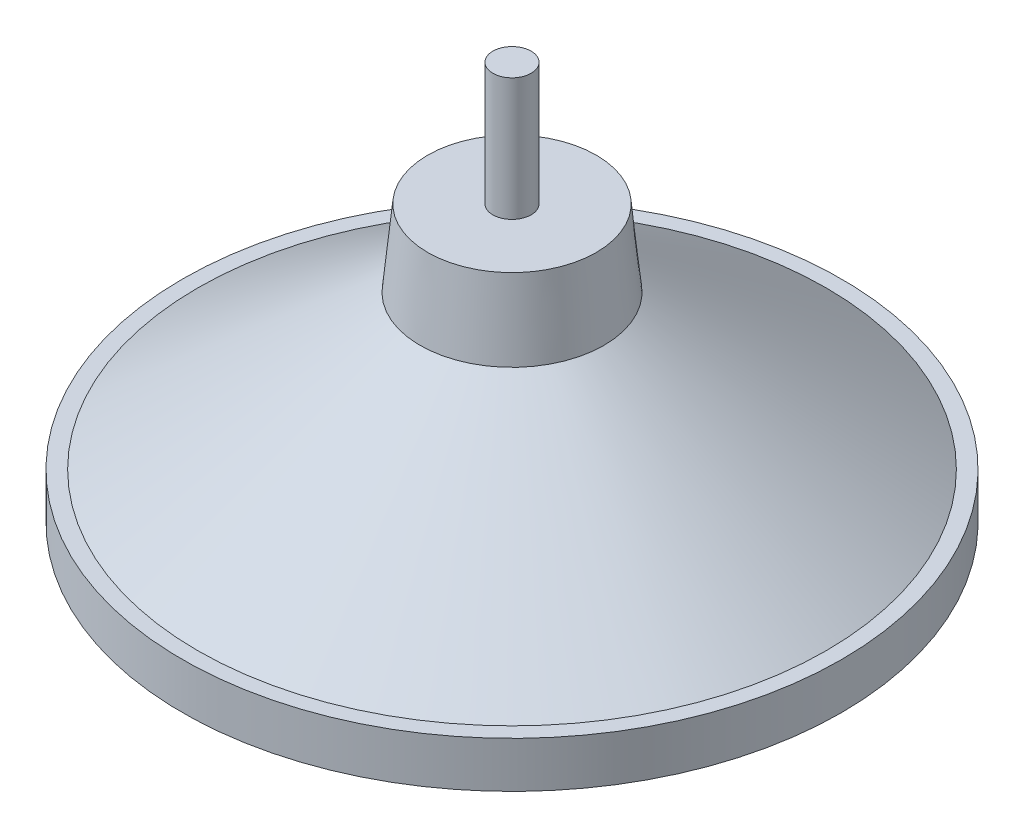
SolidWorks part; units mm, degrees
ref_plane "Front Plane" through (0, 0, 0) normal (0, 0, 1) x (1, 0, 0)
ref_plane "Top Plane" through (0, 0, 0) normal (0, 1, 0) x (1, 0, 0)
ref_plane "Right Plane" through (0, 0, 0) normal (1, 0, 0) x (0, 0, -1)
sketch "Sketch1" plane through (0, 0, 0) normal (0, 0, 1) x (1, 0, 0)
  line L0 (0, 0) -> (68.2625, 0)
  line L1 (68.2625, 0) -> (68.2625, 9.525)
  line L2 (68.2625, 9.525) -> (65.0875, 9.525)
  line L3 (65.0875, 9.525) -> (19.05, 41.275)
  line L4 (19.05, 41.275) -> (17.4625, 57.15)
  line L5 (17.4625, 57.15) -> (3.9687, 57.15)
  line L6 (0, 57.15) -> (0, 0)
  line L7 (3.9687, 57.15) -> (3.9687, 82.55)
  line L8 (3.9687, 82.55) -> (0, 82.55)
  line L9 (0, 82.55) -> (0, 57.15)
  point P3 (0, 0)
  dimension "D1" = 17.4625
  dimension "D2" = 68.2625
  dimension "D3" = 9.525
  dimension "D4" = 3.175
  dimension "D5" = 19.05
  dimension "D6" = 15.875
  dimension "D7" = 57.15
  dimension "D8" = 25.4
  dimension "D9" = 3.9688
revolve "Revolve1" add sketch "Sketch1" angle 360 about L6
